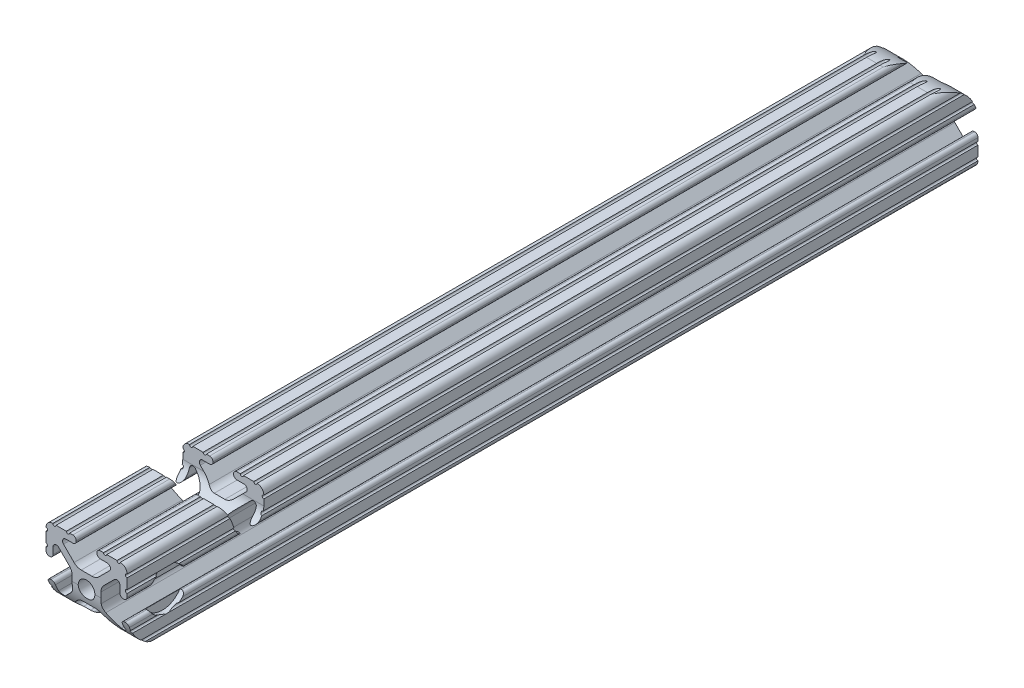
SolidWorks part; units mm, degrees
material "6063-O, Extruded Rod (SS)"
ref_plane "Front Plane" through (0, 0, 0) normal (0, 0, 1) x (1, 0, 0)
ref_plane "Top Plane" through (0, 0, 0) normal (0, 1, 0) x (1, 0, 0)
ref_plane "Right Plane" through (0, 0, 0) normal (1, 0, 0) x (0, 0, -1)
sketch "Sketch1" plane through (0, 0, 0) normal (0, 0, 1) x (1, 0, 0)
  line L88 (-7.1797, -8.6452) -> (-3.9523, -5.4237)
  line L89 (-1.7093, -4.4958) -> (1.7093, -4.4958)
  line L90 (3.9523, -5.4237) -> (7.1797, -8.6452)
  line L91 (6.4164, -10.4902) -> (4.2875, -10.4902)
  line L92 (3.2385, -11.5392) -> (3.2385, -11.651)
  line L93 (4.2875, -12.7) -> (5.3171, -12.7)
  line L94 (6.3331, -12.7) -> (9.5504, -12.7)
  line L95 (12.7, -9.5504) -> (12.7, -6.3331)
  line L96 (12.7, -5.3171) -> (12.7, -4.2875)
  line L97 (11.651, -3.2385) -> (11.5392, -3.2385)
  line L98 (10.4902, -4.2875) -> (10.4902, -6.4021)
  line L99 (8.7371, -7.1294) -> (5.441, -3.8408)
  line L100 (4.5085, -1.5932) -> (4.5085, 1.5932)
  line L101 (5.441, 3.8408) -> (8.7371, 7.1294)
  line L102 (10.4902, 6.4021) -> (10.4902, 4.2875)
  line L103 (11.5392, 3.2385) -> (11.651, 3.2385)
  line L104 (12.7, 4.2875) -> (12.7, 5.3171)
  line L105 (12.7, 6.3331) -> (12.7, 9.5504)
  line L106 (9.5504, 12.7) -> (6.3331, 12.7)
  line L107 (5.3171, 12.7) -> (4.2875, 12.7)
  line L108 (3.2385, 11.651) -> (3.2385, 11.5392)
  line L109 (4.2875, 10.4902) -> (6.4768, 10.4902)
  line L110 (7.207, 8.7244) -> (3.8983, 5.4232)
  line L111 (1.6558, 4.4958) -> (-1.6558, 4.4958)
  line L112 (-3.8983, 5.4232) -> (-7.207, 8.7244)
  line L113 (-6.4768, 10.4902) -> (-4.2875, 10.4902)
  line L114 (-3.2385, 11.5392) -> (-3.2385, 11.651)
  line L115 (-4.2875, 12.7) -> (-5.3171, 12.7)
  line L116 (-6.3331, 12.7) -> (-9.5504, 12.7)
  line L117 (-12.7, 9.5504) -> (-12.7, 6.3331)
  line L118 (-12.7, 5.3171) -> (-12.7, 4.2875)
  line L119 (-11.651, 3.2385) -> (-11.5392, 3.2385)
  line L120 (-10.4902, 4.2875) -> (-10.4902, 6.4021)
  line L121 (-8.7371, 7.1294) -> (-5.441, 3.8408)
  line L122 (-4.5085, 1.5932) -> (-4.5085, -1.5932)
  line L123 (-5.441, -3.8408) -> (-8.7371, -7.1294)
  line L124 (-10.4902, -6.4021) -> (-10.4902, -4.2875)
  line L125 (-11.5392, -3.2385) -> (-11.651, -3.2385)
  line L126 (-12.7, -4.2875) -> (-12.7, -5.3171)
  line L127 (-12.7, -6.3331) -> (-12.7, -9.5504)
  line L128 (-9.5504, -12.7) -> (-6.3331, -12.7)
  line L129 (-5.3171, -12.7) -> (-4.2875, -12.7)
  line L130 (-3.2385, -11.651) -> (-3.2385, -11.5392)
  line L131 (-4.2875, -10.4902) -> (-6.4164, -10.4902)
  circle A1 centre (0, 0) radius 2.6035
  arc A104 (-7.1797, -8.6452) -> (-6.4164, -10.4902) centre (-6.4164, -9.4098) ccw
  arc A105 (-1.7093, -4.4958) -> (-3.9523, -5.4237) centre (-1.7093, -7.6708) ccw
  arc A106 (3.9523, -5.4237) -> (1.7093, -4.4958) centre (1.7093, -7.6708) ccw
  arc A107 (6.4164, -10.4902) -> (7.1797, -8.6452) centre (6.4164, -9.4098) ccw
  arc A108 (4.2875, -10.4902) -> (3.2385, -11.5392) centre (4.2875, -11.5392) ccw
  arc A109 (3.2385, -11.651) -> (4.2875, -12.7) centre (4.2875, -11.651) ccw
  arc A110 (6.3331, -12.7) -> (5.3171, -12.7) centre (5.8251, -12.7) ccw
  arc A111 (10.5664, -12.6998) -> (9.5504, -12.7) centre (10.0584, -12.7) ccw
  arc A112 (10.5664, -12.6998) -> (12.6998, -10.5664) centre (10.5918, -10.5918) ccw
  arc A113 (12.7, -9.5504) -> (12.6998, -10.5664) centre (12.7, -10.0584) ccw
  arc A114 (12.7, -5.3171) -> (12.7, -6.3331) centre (12.7, -5.8251) ccw
  arc A115 (12.7, -4.2875) -> (11.651, -3.2385) centre (11.651, -4.2875) ccw
  arc A116 (11.5392, -3.2385) -> (10.4902, -4.2875) centre (11.5392, -4.2875) ccw
  arc A117 (8.7371, -7.1294) -> (10.4902, -6.4021) centre (9.4628, -6.4021) ccw
  arc A118 (4.5085, -1.5932) -> (5.441, -3.8408) centre (7.6835, -1.5932) ccw
  arc A119 (5.441, 3.8408) -> (4.5085, 1.5932) centre (7.6835, 1.5932) ccw
  arc A120 (10.4902, 6.4021) -> (8.7371, 7.1294) centre (9.4628, 6.4021) ccw
  arc A121 (10.4902, 4.2875) -> (11.5392, 3.2385) centre (11.5392, 4.2875) ccw
  arc A122 (11.651, 3.2385) -> (12.7, 4.2875) centre (11.651, 4.2875) ccw
  arc A123 (12.7, 6.3331) -> (12.7, 5.3171) centre (12.7, 5.8251) ccw
  arc A124 (12.6998, 10.5664) -> (12.7, 9.5504) centre (12.7, 10.0584) ccw
  arc A125 (12.6998, 10.5664) -> (10.5664, 12.6998) centre (10.5918, 10.5918) ccw
  arc A126 (9.5504, 12.7) -> (10.5664, 12.6998) centre (10.0584, 12.7) ccw
  arc A127 (5.3171, 12.7) -> (6.3331, 12.7) centre (5.8251, 12.7) ccw
  arc A128 (4.2875, 12.7) -> (3.2385, 11.651) centre (4.2875, 11.651) ccw
  arc A129 (3.2385, 11.5392) -> (4.2875, 10.4902) centre (4.2875, 11.5392) ccw
  arc A130 (7.207, 8.7244) -> (6.4768, 10.4902) centre (6.4768, 9.4563) ccw
  arc A131 (1.6558, 4.4958) -> (3.8983, 5.4232) centre (1.6558, 7.6708) ccw
  arc A132 (-3.8983, 5.4232) -> (-1.6558, 4.4958) centre (-1.6558, 7.6708) ccw
  arc A133 (-6.4768, 10.4902) -> (-7.207, 8.7244) centre (-6.4768, 9.4563) ccw
  arc A134 (-4.2875, 10.4902) -> (-3.2385, 11.5392) centre (-4.2875, 11.5392) ccw
  arc A135 (-3.2385, 11.651) -> (-4.2875, 12.7) centre (-4.2875, 11.651) ccw
  arc A136 (-6.3331, 12.7) -> (-5.3171, 12.7) centre (-5.8251, 12.7) ccw
  arc A137 (-10.5664, 12.6998) -> (-9.5504, 12.7) centre (-10.0584, 12.7) ccw
  arc A138 (-10.5664, 12.6998) -> (-12.6998, 10.5664) centre (-10.5918, 10.5918) ccw
  arc A139 (-12.7, 9.5504) -> (-12.6998, 10.5664) centre (-12.7, 10.0584) ccw
  arc A140 (-12.7, 5.3171) -> (-12.7, 6.3331) centre (-12.7, 5.8251) ccw
  arc A141 (-12.7, 4.2875) -> (-11.651, 3.2385) centre (-11.651, 4.2875) ccw
  arc A142 (-11.5392, 3.2385) -> (-10.4902, 4.2875) centre (-11.5392, 4.2875) ccw
  arc A143 (-8.7371, 7.1294) -> (-10.4902, 6.4021) centre (-9.4628, 6.4021) ccw
  arc A144 (-4.5085, 1.5932) -> (-5.441, 3.8408) centre (-7.6835, 1.5932) ccw
  arc A145 (-5.441, -3.8408) -> (-4.5085, -1.5932) centre (-7.6835, -1.5932) ccw
  arc A146 (-10.4902, -6.4021) -> (-8.7371, -7.1294) centre (-9.4628, -6.4021) ccw
  arc A147 (-10.4902, -4.2875) -> (-11.5392, -3.2385) centre (-11.5392, -4.2875) ccw
  arc A148 (-11.651, -3.2385) -> (-12.7, -4.2875) centre (-11.651, -4.2875) ccw
  arc A149 (-12.7, -6.3331) -> (-12.7, -5.3171) centre (-12.7, -5.8251) ccw
  arc A150 (-12.6998, -10.5664) -> (-12.7, -9.5504) centre (-12.7, -10.0584) ccw
  arc A151 (-12.6998, -10.5664) -> (-10.5664, -12.6998) centre (-10.5918, -10.5918) ccw
  arc A152 (-9.5504, -12.7) -> (-10.5664, -12.6998) centre (-10.0584, -12.7) ccw
  arc A153 (-5.3171, -12.7) -> (-6.3331, -12.7) centre (-5.8251, -12.7) ccw
  arc A154 (-4.2875, -12.7) -> (-3.2385, -11.651) centre (-4.2875, -11.651) ccw
  arc A155 (-3.2385, -11.5392) -> (-4.2875, -10.4902) centre (-4.2875, -11.5392) ccw
extrude "Boss-Extrude1" add sketch "Sketch1" along normal mid plane 266.7
sketch "Sketch2" plane through (4.5085, 0, 0) normal (1, 0, 0) x (0, 0, -1)
  line L0 (-133.35, -1.5932) -> (-133.35, 1.5932) construction
  line L1 (-133.35, -12.6998) -> (133.35, -12.6998) construction
  circle A0 centre (-120.65, 0) radius 3.175
  dimension "D1" = 6.35
  dimension "D2" = 12.7
  dimension "D3" = 12.6998
extrude "Cut-Extrude1" cut sketch "Sketch2" against normal through all both and the other way through all
sketch "Sketch3" plane through (12.7, 0, 0) normal (1, 0, 0) x (0, 0, -1)
  circle A0 centre (-120.65, 0) radius 6.35
  circle A1 centre (-120.65, 0) radius 3.175 construction
  dimension "D1" = 12.7
extrude "Cut-Extrude2" cut sketch "Sketch3" against normal blind 1.5875
extrude "Cut-Extrude3" cut sketch "Sketch3<2>" along normal blind 1.5875 from surface starting at face at (-12.7, -7.9417, 0)
sketch "Sketch3<2>" plane through (12.7, 0, 0) normal (1, 0, 0) x (0, 0, -1) same geometry as "Sketch3"
sketch "Sketch4" plane through (12.7, 0, 0) normal (1, 0, 0) x (0, 0, -1)
  line L0 (-133.35, 6.3331) -> (-133.35, 9.5504) construction
  line L1 (-133.35, -1.5932) -> (-133.35, 1.5932) construction
  line L2 (-100.0125, 7.62) -> (-100.0125, 12.7)
  line L3 (-100.0125, 12.7) -> (-90.4875, 12.7)
  line L4 (-90.4875, 12.7) -> (-90.4875, 7.62)
  line L5 (-133.35, 12.7) -> (133.35, 12.7) construction
  line L6 (-100.0125, 7.62) -> (-90.4875, 7.62)
  circle A0 centre (-95.25, 7.62) radius 4.7625
  point P6 (-133.35, 0)
  line M4 (-120.1868, 6.3331) -> (133.35, 6.3331)
  line M6 (133.35, 9.5504) -> (-133.35, 9.5504)
  dimension "D3" = 9.525
  dimension "D1" = 38.1
  dimension "D2" = 7.62
extrude "Cut-Extrude4" cut sketch "Sketch4" against normal through all contours A0 L4 L3 L2 M6 | A0 L2 M6 | L6 A0 M6 | A0 M6 | A0 L4 M6 | L6 A0 M4 | A0 M4 region at (12.7, 8.5711, 95.25) region at (12.7, 9.072, 99.8908) region at (12.7, 6.9806, 95.25) region at (12.7, 11.1252, 99.9122) region at (12.7, 9.072, 90.6092) region at (12.7, 10.7182, 95.25) region at (12.7, 4.8875, 95.25)
sketch "Sketch5" plane through (12.7, 0, 0) normal (1, 0, 0) x (0, 0, -1)
  line L3 (-133.35, -12.7) -> (-120.65, -12.7)
  line L4 (-133.35, -12.7) -> (133.35, -12.7) construction
  line L6 (-133.35, -12.7) -> (-133.35, 0)
  arc A1 (-133.35, 0) -> (-120.65, -12.7) centre (-120.65, 0) ccw
  line M6 (-100.0125, 9.5504) -> (-133.35, 9.5504)
  line M8 (-133.35, 6.3331) -> (-121.1132, 6.3331)
extrude "Cut-Extrude5" cut sketch "Sketch5" against normal through all contours L3 | M8 | M6 region at (12.7, -9.8632, 130.5132)
sketch "Sketch6" plane through (12.7, 0, 0) normal (1, 0, 0) x (0, 0, -1)
  line L0 (-102.9845, 12.7) -> (-95.25, 12.7)
  line L1 (-100.0125, 12.7) -> (-133.35, 12.7) construction
  line L2 (-95.25, 12.7) -> (-95.25, 12.3825)
  circle A0 centre (-120.65, 0) radius 26.5184 construction
  circle A1 centre (-95.25, 7.62) radius 4.7625
  arc A2 (-91.8477, 4.2875) -> (-91.0813, 5.3171) centre (-95.25, 7.62) ccw construction
  circle A3 centre (-120.65, 0) radius 31.2809 construction
  circle A4 centre (-120.65, 0) radius 21.7568 construction
  arc A5 (-102.9845, 12.7) -> (-99.7865, 6.1704) centre (-120.65, 0) cw
  arc M11 (-99.8353, 6.3331) -> (-100.0125, 7.62) centre (-95.25, 7.62) cw
  line M12 (-100.0125, 7.62) -> (-100.0125, 9.5504)
  line M13 (-100.0125, 9.5504) -> (-133.35, 9.5504)
extrude "Cut-Extrude6" cut sketch "Sketch6" against normal through all contours L0 A5 A1 L2 M13 M12 | A5 M13 M11 M12 region at (12.7, 11.4936, 99.8376) region at (12.7, 8.6597, 100.3572)
sketch "Sketch7" plane through (-12.7, 0, 0) normal (-1, 0, 0) x (0, 0, 1)
  line L0 (-133.35, 1.5932) -> (-133.35, -1.5932) construction
  line L2 (-133.35, 0) -> (-133.35, 12.7)
  line L3 (-133.35, 12.7) -> (-120.65, 12.7)
  line L4 (90.4875, 12.7) -> (-133.35, 12.7) construction
  arc A0 (-133.35, 0) -> (-120.65, 12.7) centre (-120.65, 0) cw
extrude "Cut-Extrude7" cut sketch "Sketch7" against normal through all
